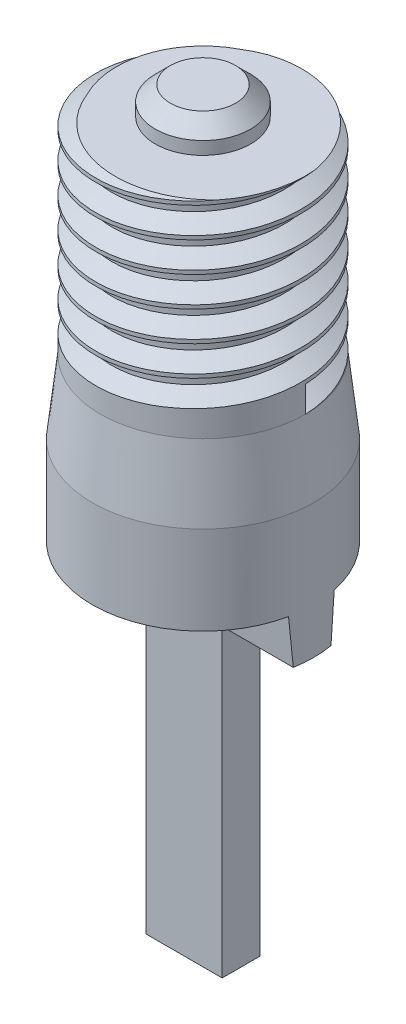
SolidWorks part; units mm, degrees
other "DetailItem1"
ref_plane "Front Plane" through (0, 0, 0) normal (0, 0, 1) x (1, 0, 0)
ref_plane "Top Plane" through (0, 0, 0) normal (0, 1, 0) x (1, 0, 0)
ref_plane "Right Plane" through (0, 0, 0) normal (1, 0, 0) x (0, 0, -1)
ref_plane "Plane1" through (0, 0, 0) normal (1, 0, 0) x (0, 0, -1)
sketch "Sketch1" plane through (0, 0, 0) normal (1, 0, 0) x (0, 0, -1)
  line L0 (5.3467, 29.6164) -> (5.3467, 25.7877)
  line L1 (5.3467, 25.7877) -> (4.8398, 25.316)
  line L2 (4.8398, 25.316) -> (3.899, 10.6934)
  line L3 (3.899, 10.6934) -> (3.6957, 10.6934)
  line L4 (3.6957, 10.6934) -> (3.6957, 6.2738)
  line L5 (3.6957, 6.2738) -> (0, 6.2738)
  line L6 (0, 6.2738) -> (0, 30.8864)
  line L7 (0, 6.2738) -> (0, 30.8864) construction
  arc A0 (0, 30.8864) -> (5.3467, 29.6164) centre (0, 18.9966) cw
revolve "Revolve1" add sketch "Sketch1" angle 360 about L7 reverse direction yes
ref_plane "Plane2" through (0, 0, 0) normal (1, 0, 0) x (0, 0, -1)
sketch "Sketch2" plane through (0, 0, 0) normal (1, 0, 0) x (0, 0, -1)
  line L0 (-3.6957, 5.1562) -> (3.6957, 5.1562)
  line L1 (3.6957, 5.1562) -> (3.6957, 8.2042)
  line L2 (3.6957, 8.2042) -> (0.762, 8.2042)
  line L3 (0.762, 8.2042) -> (0.6287, 6.6802)
  line L4 (0.6287, 6.6802) -> (-0.6287, 6.6802)
  line L5 (-0.6287, 6.6802) -> (-0.762, 8.2042)
  line L6 (-0.762, 8.2042) -> (-3.6957, 8.2042)
  line L7 (-3.6957, 8.2042) -> (-3.6957, 5.1562)
extrude "Cut-Extrude1" cut sketch "Sketch2" against normal blind 12 and the other way blind 12
ref_plane "Plane3" through (0, 0, 0) normal (1, 0, 0) x (0, 0, -1)
sketch "Sketch3" plane through (0, 0, 0) normal (1, 0, 0) x (0, 0, -1)
  line L0 (-0.6287, 6.6802) -> (-0.6287, -3.4798)
  line L1 (-0.6287, -3.4798) -> (0.6287, -3.4798)
  line L2 (0.6287, -3.4798) -> (0.6287, 6.6802)
  line L3 (0.6287, 6.6802) -> (-0.6287, 6.6802)
extrude "Boss-Extrude1" add sketch "Sketch3" against normal blind 1.27 and the other way blind 1.27
sketch "Sketch4" plane through (0, 10.6934, 0) normal (0, -1, 0) x (1, 0, 0)
  circle A0 centre (0, 0) radius 5.3467 construction
  circle A1 centre (0, 0) radius 5.3467
extrude "Cut-Extrude2" cut sketch "Sketch4" against normal up to next
sketch "Sketch5" plane through (0, 0, 0) normal (1, 0, 0) x (0, 0, -1)
  line L0 (0, 8.2042) -> (0, 21.3942) construction
  line L2 (-3.6957, 8.2042) -> (-0.762, 8.2042) construction
  line L3 (0, 21.3942) -> (1.59, 21.3942)
  line L4 (1.59, 21.3942) -> (1.59, 20.4642)
  line L5 (1.59, 20.4642) -> (3.425, 20.4642)
  line L6 (3.425, 20.4642) -> (3.425, 13.5742)
  line L7 (3.425, 13.5742) -> (3.6957, 11.1542)
  line L8 (3.6957, 11.1542) -> (3.6957, 8.2042)
  line L9 (3.6957, 8.2042) -> (0, 8.2042)
  line L10 (0, 21.3942) -> (0, 8.2042)
  dimension "D1" = 13.19
  dimension "D2" = 3.18
  dimension "D3" = 0.93
  dimension "D4" = 6.85
  dimension "D5" = 6.89
  dimension "D6" = 2.95
revolve "Revolve2" add sketch "Sketch5" angle 360 about L0
chamfer "Chamfer1" distance 0.5 angle 45 1 edges at (0, 21.3942, -1.59)
thread "Thread1" pitch 1 method cut trim with end face yes profile "Thread Profile2" start angle 0, offset 0, length 0, pitch 1, diameter 6.85
ref_plane "Plane5" through (3.425, 13.5742, 0) normal (0, 0, 1) x (1, 0, 0)
sketch "Thread Profile2" plane through (3.425, 13.5742, 0) normal (0, 0, 1) x (1, 0, 0)
  line L0 (0, 0) -> (0, 1) construction
  line L11 (0, 0) -> (0, 0.875)
  line L12 (0, 0.875) -> (-0.5413, 0.5625)
  line L13 (-0.5413, 0.5625) -> (-0.5413, 0.3125)
  line L15 (-0.5413, 0.3125) -> (0, 0)
  line L17 (-0.5413, 0.4375) -> (0, 0.4375) construction
  point P2 (0, 0)
  dimension "Pitch" = 1
  dimension "Profile_Angle" = 60
  dimension "Profile_Land" = 0.25
  dimension "Profile_Height" = 0.5413
